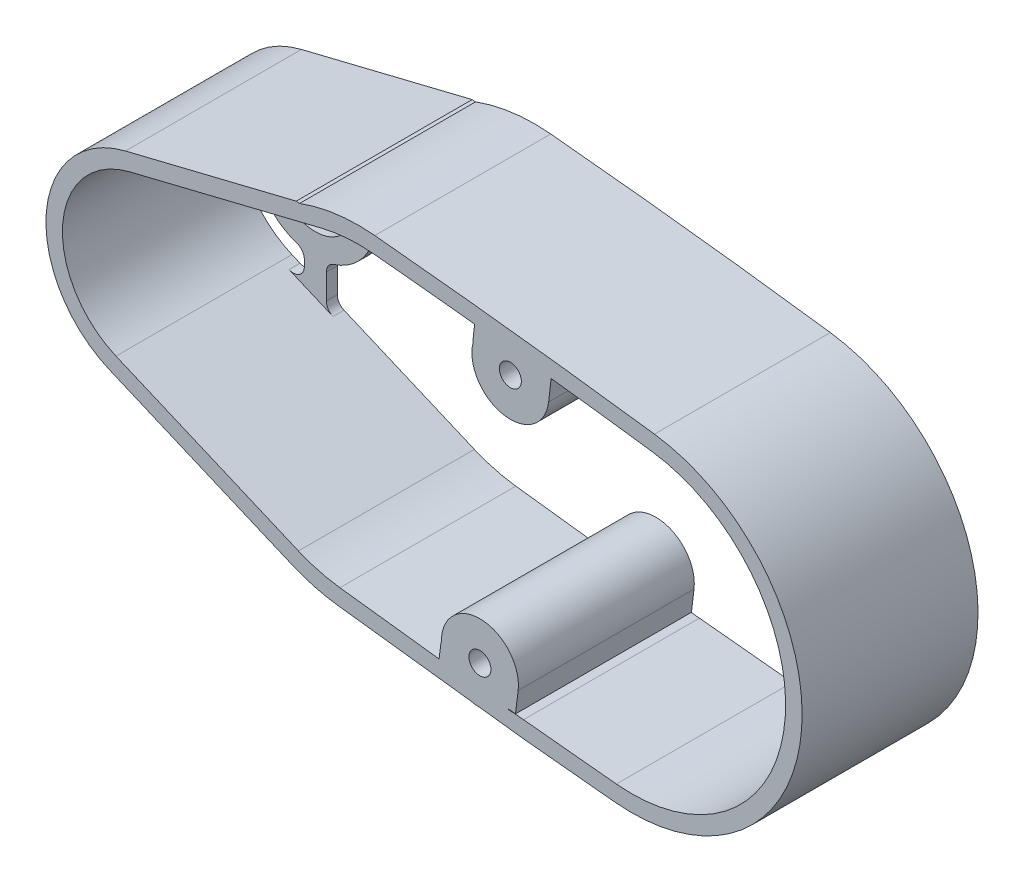
SolidWorks part; units mm, degrees
ref_plane "Front Plane" through (0, 0, 0) normal (0, 0, 1) x (1, 0, 0)
ref_plane "Top Plane" through (0, 0, 0) normal (0, 1, 0) x (1, 0, 0)
ref_plane "Right Plane" through (0, 0, 0) normal (1, 0, 0) x (0, 0, -1)
sketch "Sketch1" plane through (0, 0, 0) normal (0, 0, 1) x (1, 0, 0)
  line L0 (-84.7001, 45.2979) -> (-76.2553, 46.1432)
  line L1 (-106.5406, -27.8625) -> (-106.5406, -50)
  line L2 (-104.1975, -55.6569) -> (-94.1975, -65.6569)
  line L3 (-88.5406, -68) -> (-49.4485, -68)
  line L4 (49.4485, -68) -> (88.5406, -68)
  line L5 (94.1975, -65.6569) -> (104.1975, -55.6569)
  line L6 (106.5406, -50) -> (106.5406, -27.8625)
  line L7 (76.2553, 46.1432) -> (84.7001, 45.2979)
  line L8 (-88.5406, -69.5) -> (-49.4485, -69.5)
  line L9 (49.4485, -69.5) -> (88.5406, -69.5)
  line L10 (95.2581, -66.7175) -> (105.2581, -56.7175)
  line L11 (108.0406, -50) -> (108.0406, -27.8625)
  line L12 (76.1059, 44.6507) -> (84.5506, 43.8053)
  line L13 (-84.5506, 43.8053) -> (-76.1059, 44.6507)
  line L14 (-108.0406, -27.8625) -> (-108.0406, -50)
  line L15 (-105.2581, -56.7175) -> (-95.2581, -66.7175)
  line L16 (-88.5406, -69.5) -> (-49.4485, -69.5)
  line L17 (49.4485, -69.5) -> (88.5406, -69.5)
  line L18 (95.2581, -66.7175) -> (105.2581, -56.7175)
  line L19 (108.0406, -50) -> (108.0406, -27.8625)
  line L20 (76.1059, 44.6507) -> (84.5506, 43.8053)
  line L21 (-84.5506, 43.8053) -> (-76.1059, 44.6507)
  line L22 (-108.0406, -27.8625) -> (-108.0406, -50)
  line L23 (-105.2581, -56.7175) -> (-95.2581, -66.7175)
  line L24 (40.0545, 72.8358) -> (57.5617, 77.1367)
  line L25 (38.6068, 54.8662) -> (55.1996, 47.818)
  line L26 (87.9632, 73.103) -> (88.1635, 74.5895) construction
  line L27 (34.3209, 63.6101) -> (32.8209, 63.6101) construction
  line L28 (40.4123, 71.3791) -> (57.9195, 75.68)
  line L29 (39.1932, 56.2468) -> (55.7861, 49.1986)
  line L30 (76.2553, 46.1432) -> (59.5577, 48.1881)
  line L31 (76.1059, 44.6507) -> (59.3757, 46.6992)
  line L32 (61.2596, 62.0843) -> (86.0945, 59.2282) construction
  line L33 (73.6771, 60.6563) -> (75.2904, 74.6849) construction
  line L34 (78.539, 72.2982) -> (78.7664, 74.2758)
  line L35 (71.5848, 73.0979) -> (71.8122, 75.0756)
  line L36 (68.8182, 49.04) -> (68.5785, 47.0834)
  line L37 (72.2922, 48.6145) -> (72.0526, 46.6579) construction
  line L38 (75.7663, 48.1891) -> (75.5266, 46.2324)
  arc A0 (87.9632, 73.103) -> (-87.9632, 73.103) centre (0, -580) ccw
  arc A1 (-87.9632, 73.103) -> (-84.7001, 45.2979) centre (-86.0945, 59.2282) ccw
  arc A2 (-69.7132, -15.896) -> (-76.2553, 46.1432) centre (-73.1485, 15.1063) ccw
  arc A3 (-69.7132, -15.896) -> (-99.8019, -19.9626) centre (0, -645.0455) ccw
  arc A4 (-99.8019, -19.9626) -> (-106.5406, -27.8625) centre (-98.5406, -27.8625) ccw
  arc A5 (-106.5406, -50) -> (-104.1975, -55.6569) centre (-98.5406, -50) ccw
  arc A6 (-94.1975, -65.6569) -> (-88.5406, -68) centre (-88.5406, -60) ccw
  arc A7 (-49.4485, -68) -> (-43.8792, -65.2406) centre (-49.4485, -61) ccw
  arc A8 (43.8792, -65.2406) -> (-43.8792, -65.2406) centre (0, -98.6511) ccw
  arc A9 (43.8792, -65.2406) -> (49.4485, -68) centre (49.4485, -61) ccw
  arc A10 (88.5406, -68) -> (94.1975, -65.6569) centre (88.5406, -60) ccw
  arc A11 (104.1975, -55.6569) -> (106.5406, -50) centre (98.5406, -50) ccw
  arc A12 (106.5406, -27.8625) -> (99.8019, -19.9626) centre (98.5406, -27.8625) ccw
  arc A13 (99.8019, -19.9626) -> (69.7132, -15.896) centre (0, -645.0455) ccw
  arc A14 (76.2553, 46.1432) -> (69.7132, -15.896) centre (73.1485, 15.1063) ccw
  arc A15 (84.7001, 45.2979) -> (87.9632, 73.103) centre (86.0945, 59.2282) ccw
  arc A16 (-49.4485, -69.5) -> (-42.6858, -66.1493) centre (-49.4485, -61) ccw
  arc A17 (42.6858, -66.1493) -> (-42.6858, -66.1493) centre (0, -98.6511) ccw
  arc A18 (42.6858, -66.1493) -> (49.4485, -69.5) centre (49.4485, -61) ccw
  arc A19 (88.5406, -69.5) -> (95.2581, -66.7175) centre (88.5406, -60) ccw
  arc A20 (105.2581, -56.7175) -> (108.0406, -50) centre (98.5406, -50) ccw
  arc A21 (108.0406, -27.8625) -> (100.0384, -18.4814) centre (98.5406, -27.8625) ccw
  arc A22 (100.0384, -18.4814) -> (69.8784, -14.4051) centre (0, -645.0455) ccw
  arc A23 (76.1059, 44.6507) -> (69.8784, -14.4051) centre (73.1485, 15.1063) ccw
  arc A24 (84.5506, 43.8053) -> (88.1635, 74.5895) centre (86.0945, 59.2282) ccw
  arc A25 (88.1635, 74.5895) -> (-88.1635, 74.5895) centre (0, -580) ccw
  arc A26 (-88.1635, 74.5895) -> (-84.5506, 43.8053) centre (-86.0945, 59.2282) ccw
  arc A27 (-69.8784, -14.4051) -> (-76.1059, 44.6507) centre (-73.1485, 15.1063) ccw
  arc A28 (-69.8784, -14.4051) -> (-100.0384, -18.4814) centre (0, -645.0455) ccw
  arc A29 (-100.0384, -18.4814) -> (-108.0406, -27.8625) centre (-98.5406, -27.8625) ccw
  arc A30 (-108.0406, -50) -> (-105.2581, -56.7175) centre (-98.5406, -50) ccw
  arc A31 (-95.2581, -66.7175) -> (-88.5406, -69.5) centre (-88.5406, -60) ccw
  arc A32 (-49.4485, -69.5) -> (-42.6858, -66.1493) centre (-49.4485, -61) ccw
  arc A33 (42.6858, -66.1493) -> (-42.6858, -66.1493) centre (0, -98.6511) ccw
  arc A34 (42.6858, -66.1493) -> (49.4485, -69.5) centre (49.4485, -61) ccw
  arc A35 (88.5406, -69.5) -> (95.2581, -66.7175) centre (88.5406, -60) ccw
  arc A36 (105.2581, -56.7175) -> (108.0406, -50) centre (98.5406, -50) ccw
  arc A37 (108.0406, -27.8625) -> (100.0384, -18.4814) centre (98.5406, -27.8625) ccw
  arc A38 (100.0384, -18.4814) -> (69.8784, -14.4051) centre (0, -645.0455) ccw
  arc A39 (76.1059, 44.6507) -> (69.8784, -14.4051) centre (73.1485, 15.1063) ccw
  arc A40 (84.5506, 43.8053) -> (88.1635, 74.5895) centre (86.0945, 59.2282) ccw
  arc A41 (88.1635, 74.5895) -> (-88.1635, 74.5895) centre (0, -580) ccw
  arc A42 (-88.1635, 74.5895) -> (-84.5506, 43.8053) centre (-86.0945, 59.2282) ccw
  arc A43 (-69.8784, -14.4051) -> (-76.1059, 44.6507) centre (-73.1485, 15.1063) ccw
  arc A44 (-69.8784, -14.4051) -> (-100.0384, -18.4814) centre (0, -645.0455) ccw
  arc A45 (-100.0384, -18.4814) -> (-108.0406, -27.8625) centre (-98.5406, -27.8625) ccw
  arc A46 (-108.0406, -50) -> (-105.2581, -56.7175) centre (-98.5406, -50) ccw
  arc A47 (-95.2581, -66.7175) -> (-88.5406, -69.5) centre (-88.5406, -60) ccw
  circle A48 centre (42.3209, 63.6101) radius 3.5 construction
  circle A49 centre (61.2596, 62.0843) radius 8 construction
  circle A50 centre (86.0945, 59.2282) radius 8 construction
  circle A51 centre (42.3209, 63.6101) radius 3.5
  circle A52 centre (61.2596, 62.0843) radius 8
  circle A53 centre (86.0945, 59.2282) radius 8
  circle A54 centre (42.3209, 63.6101) radius 9.5
  circle A55 centre (61.2596, 62.0843) radius 15.5
  circle A56 centre (42.3209, 63.6101) radius 8
  circle A57 centre (61.2596, 62.0843) radius 14
  circle A58 centre (75.0619, 72.698) radius 1
  circle A59 centre (75.0619, 72.698) radius 3.5
  circle A60 centre (72.2922, 48.6145) radius 1
  circle A61 centre (72.2922, 48.6145) radius 3.5
  point P110 (75.1761, 73.6915)
  dimension "D3" = 6
  dimension "D5" = 2
  dimension "D4" = 1
  dimension "D1" = 0
  dimension "D2" = 1.5
extrude "Boss-Extrude1" add sketch "Sketch1" along normal blind 16 contours A14 A61 L31 L20 A40 A41 A59 A0 A15 L7 | A59 L34 A0 | A59 A0 L35 A55 | A59 A41 A55 A0 | A0 A55 | A57 A0 A55 L28 | A55 A0 L24 A54 L28 | A56 L28 A54 L29 | A55 L29 A54 L25 | A57 L29 A55 L30 | A14 A61 L30 A55 L31 | L31 A61 A14 | L30 A61 A55 | L38 A61 L30 | A61 L31 | A59 | A58 | A61 | A60 region at (48.4827, 74.2503, 0) region at (42.728, 72.8733, 0) region at (62.6458, 76.6141, 0) region at (55.8246, 75.6516, 0) region at (46.7339, 52.1031, 0) region at (70.1214, 76.1622, 0) region at (57.5588, 48.271, 0) region at (81.7623, 74.9794, 0) region at (66.2592, 46.5236, 0) region at (78.5282, 73.8128, 0) region at (71.9433, 74.5862, 0) region at (69.3498, 45.7091, 0) region at (71.8689, 45.1578, 0) region at (68.8159, 47.5227, 0) region at (75.4075, 46.7345, 0)
sketch "Sketch2" plane through (0, 0, 0) normal (0, 0, -1) x (-1, 0, 0)
  line L0 (-42.3209, 63.6101) -> (-34.3209, 63.6101) construction
  line L1 (-45.8209, 63.6101) -> (-47.8209, 63.6101) construction
  line L2 (-34.3209, 64.6101) -> (-36.9126, 64.6101)
  line L3 (-34.3209, 64.6101) -> (-34.3209, 62.6101)
  line L4 (-34.3209, 62.6101) -> (-36.9126, 62.6101)
  line L5 (-36.9126, 64.6101) -> (-36.9126, 62.6101)
  line L6 (-34.3209, 64.6101) -> (-36.9126, 62.6101) construction
  line L7 (-34.3209, 62.6101) -> (-36.9126, 64.6101) construction
  line L8 (-42.3209, 69.1101) -> (-42.3209, 71.848) construction
  line L9 (-78.539, 72.2982) -> (-78.7664, 74.2758)
  line L10 (-84.7001, 45.2979) -> (-76.2553, 46.1432)
  line L11 (-74.9232, 46.3063) -> (-75.5266, 46.2324)
  line L12 (-75.5266, 46.2324) -> (-75.7663, 48.1891)
  line L13 (-68.7541, 48.5166) -> (-68.5785, 47.0834)
  line L14 (-68.5785, 47.0834) -> (-59.5577, 48.1881)
  line L15 (-55.7861, 49.1986) -> (-39.1932, 56.2468)
  line L16 (-40.4123, 71.3791) -> (-57.9195, 75.68)
  line L17 (-71.8122, 75.0756) -> (-71.6418, 73.5934)
  line L18 (-78.539, 72.2982) -> (-78.7664, 74.2758)
  line L19 (-84.7001, 45.2979) -> (-76.2553, 46.1432)
  line L20 (-74.9232, 46.3063) -> (-75.5266, 46.2324)
  line L21 (-75.5266, 46.2324) -> (-75.7663, 48.1891)
  line L22 (-68.7541, 48.5166) -> (-68.5785, 47.0834)
  line L23 (-68.5785, 47.0834) -> (-59.5577, 48.1881)
  line L24 (-55.7861, 49.1986) -> (-39.1932, 56.2468)
  line L25 (-40.4123, 71.3791) -> (-57.9195, 75.68)
  line L26 (-71.8122, 75.0756) -> (-71.6418, 73.5934)
  line L27 (-42.3209, 58.1101) -> (-42.3209, 54.9183) construction
  line L29 (-41.3209, 72.0936) -> (-43.3209, 72.0936)
  line L30 (-41.3209, 72.0936) -> (-41.3209, 69.0184)
  line L31 (-41.3209, 69.0184) -> (-43.3209, 69.0184)
  line L32 (-43.3209, 72.0936) -> (-43.3209, 69.0184)
  line L33 (-41.3209, 72.0936) -> (-43.3209, 69.0184) construction
  line L34 (-41.3209, 69.0184) -> (-43.3209, 72.0936) construction
  line L35 (-41.3209, 58.2018) -> (-43.3209, 58.2018)
  line L36 (-41.3209, 58.2018) -> (-41.3209, 54.4935)
  line L37 (-41.3209, 54.4935) -> (-43.3209, 54.4935)
  line L38 (-43.3209, 58.2018) -> (-43.3209, 54.4935)
  line L39 (-41.3209, 58.2018) -> (-43.3209, 54.4935) construction
  line L40 (-41.3209, 54.4935) -> (-43.3209, 58.2018) construction
  circle A0 centre (-42.3209, 63.6101) radius 3.5
  arc A1 (-39.1932, 56.2468) -> (-40.4123, 71.3791) centre (-42.3209, 63.6101) ccw construction
  circle A2 centre (-42.3209, 63.6101) radius 5.5
  arc A14 (-71.6418, 73.5934) -> (-71.6714, 73.5667) centre (-61.2596, 62.0843) ccw
  arc A15 (-78.539, 72.2982) -> (-71.6714, 73.5667) centre (-75.0619, 72.698) ccw
  arc A16 (-78.7664, 74.2758) -> (-87.9632, 73.103) centre (0, -580) ccw
  arc A17 (-87.9632, 73.103) -> (-84.7001, 45.2979) centre (-86.0945, 59.2282) ccw
  arc A18 (-74.8733, 46.2506) -> (-76.2553, 46.1432) centre (-73.1485, 15.1063) ccw
  arc A19 (-74.9232, 46.3063) -> (-74.8733, 46.2506) centre (-72.2922, 48.6145) ccw
  arc A20 (-68.7931, 48.5382) -> (-75.7663, 48.1891) centre (-72.2922, 48.6145) ccw
  arc A21 (-68.7931, 48.5382) -> (-68.7541, 48.5166) centre (-61.2596, 62.0843) ccw
  arc A22 (-59.5577, 48.1881) -> (-55.7861, 49.1986) centre (-61.2596, 62.0843) ccw
  arc A23 (-39.1932, 56.2468) -> (-40.4123, 71.3791) centre (-42.3209, 63.6101) ccw
  arc A24 (-57.9195, 75.68) -> (-62.5892, 76.021) centre (-61.2596, 62.0843) ccw
  arc A25 (-62.5892, 76.021) -> (-71.8122, 75.0756) centre (0, -580) ccw
  arc A26 (-71.6418, 73.5934) -> (-71.6714, 73.5667) centre (-61.2596, 62.0843) ccw
  arc A27 (-78.539, 72.2982) -> (-71.6714, 73.5667) centre (-75.0619, 72.698) ccw
  arc A28 (-78.7664, 74.2758) -> (-87.9632, 73.103) centre (0, -580) ccw
  arc A29 (-87.9632, 73.103) -> (-84.7001, 45.2979) centre (-86.0945, 59.2282) ccw
  arc A30 (-74.8733, 46.2506) -> (-76.2553, 46.1432) centre (-73.1485, 15.1063) ccw
  arc A31 (-74.9232, 46.3063) -> (-74.8733, 46.2506) centre (-72.2922, 48.6145) ccw
  arc A32 (-68.7931, 48.5382) -> (-75.7663, 48.1891) centre (-72.2922, 48.6145) ccw
  arc A33 (-68.7931, 48.5382) -> (-68.7541, 48.5166) centre (-61.2596, 62.0843) ccw
  arc A34 (-59.5577, 48.1881) -> (-55.7861, 49.1986) centre (-61.2596, 62.0843) ccw
  arc A35 (-39.1932, 56.2468) -> (-40.4123, 71.3791) centre (-42.3209, 63.6101) ccw
  arc A36 (-57.9195, 75.68) -> (-62.5892, 76.021) centre (-61.2596, 62.0843) ccw
  arc A37 (-62.5892, 76.021) -> (-71.8122, 75.0756) centre (0, -580) ccw
  point P8 (-35.6168, 63.6101)
  point P47 (-42.3209, 70.556)
  point P55 (0, 0)
  point P57 (0, 0)
  point P60 (-42.3209, 56.3476)
  arc M44 (-40.4123, 71.3791) -> (-39.1932, 56.2468) centre (-42.3209, 63.6101) cw
  dimension "D1" = 7
  dimension "D3" = 2
  dimension "D2" = 0
extrude "Boss-Extrude3" add sketch "Sketch2" against normal blind 1 contours A2 L30 L25 L32 | A2 L4 L2 M44 | A2 L38 L24 L36 | A2 | A0 region at (35.5967, 63.6101, 0) region at (42.3505, 70.4673, 0) region at (42.3649, 56.5202, 0)
fillet "Fillet1" radius 1 12 edges at (41.3209, 71.6023, 0.5) (41.3209, 69.0184, 0.5) (36.9126, 64.6101, 0.5) (36.9126, 62.6101, 0.5) (41.3209, 58.2018, 0.5) (41.3209, 55.343, 0.5) (43.3209, 58.2018, 0.5) (43.3209, 69.0184, 0.5) (43.3209, 72.0936, 0.5) (43.3209, 54.4935, 0.5) (34.3837, 64.6101, 0.5) (34.3837, 62.6101, 0.5)
